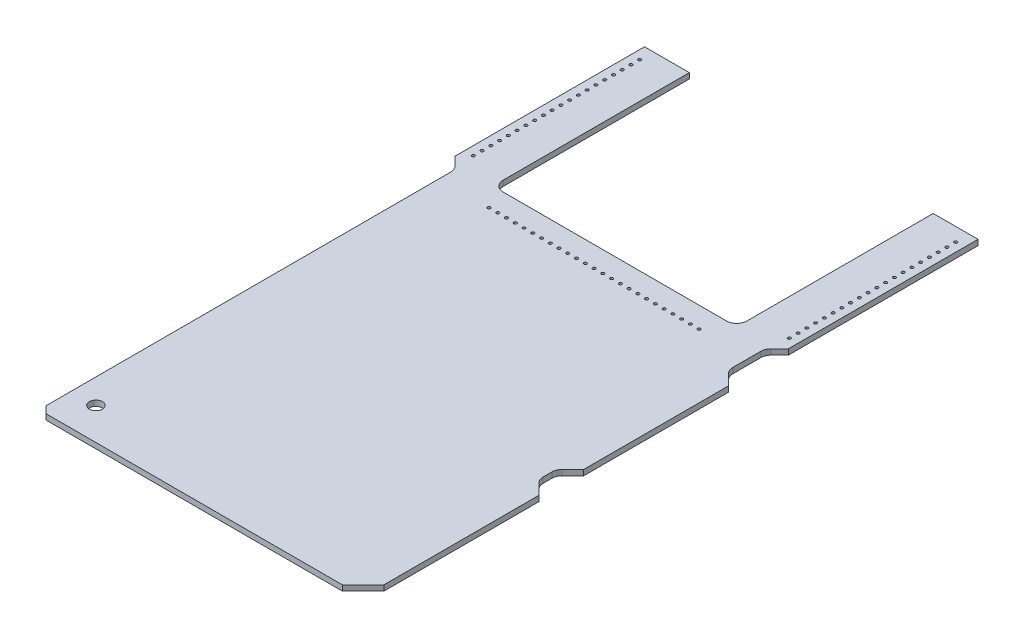
SolidWorks part; units mm, degrees
ref_plane "Front Plane" through (0, 0, 0) normal (0, 0, 1) x (1, 0, 0)
ref_plane "Top Plane" through (0, 0, 0) normal (0, 1, 0) x (1, 0, 0)
ref_plane "Right Plane" through (0, 0, 0) normal (1, 0, 0) x (0, 0, -1)
sketch "Sketch1" plane through (0, 0, 0) normal (0, 1, 0) x (1, 0, 0)
  line L1 (45, -88.5) -> (-45, -88.5)
  line L2 (45, -88.5) -> (45, 88.5)
  line L3 (45, 88.5) -> (-45, 88.5)
  line L4 (-45, -88.5) -> (-45, 88.5)
  line L5 (45, -88.5) -> (-45, 88.5) construction
  line L6 (45, 88.5) -> (-45, -88.5) construction
  point P0 (0, 0)
  dimension "D1" = 90
  dimension "D2" = 177
extrude "Boss-Extrude1" add sketch "Sketch1" along normal blind 1.6
sketch "Sketch5" plane through (0, 0, 0) normal (0, -1, 0) x (1, 0, 0)
  line L0 (45, 88.5) -> (45, -88.5) construction
  line L1 (37.6, -44) -> (37.6, -48)
  line L2 (37.6, -44) -> (22.4, -44)
  line L3 (22.4, -44) -> (22.4, -48)
  line L4 (37.6, -48) -> (22.4, -48)
  line L5 (16.1, -44) -> (16.1, -48)
  line L6 (16.1, -44) -> (0.9, -44)
  line L7 (0.9, -44) -> (0.9, -48)
  line L8 (16.1, -48) -> (0.9, -48)
  line L9 (37.6, -80) -> (37.6, -84)
  line L10 (37.6, -80) -> (22.4, -80)
  line L11 (22.4, -80) -> (22.4, -84)
  line L12 (37.6, -84) -> (22.4, -84)
  line L13 (12.1, -80) -> (12.1, -84)
  line L14 (12.1, -80) -> (-3.1, -80)
  line L15 (-3.1, -80) -> (-3.1, -84)
  line L16 (12.1, -84) -> (-3.1, -84)
  line L17 (2.025, -44.54) -> (14.975, -44.54)
  line L18 (2.025, -44.54) -> (2.025, -47.46)
  line L19 (2.025, -47.46) -> (14.975, -47.46)
  line L20 (14.975, -44.54) -> (14.975, -47.46)
  line L21 (23.525, -44.54) -> (36.475, -44.54)
  line L22 (23.525, -44.54) -> (23.525, -47.46)
  line L23 (23.525, -47.46) -> (36.475, -47.46)
  line L24 (36.475, -44.54) -> (36.475, -47.46)
  line L25 (-1.975, -80.54) -> (10.975, -80.54)
  line L26 (-1.975, -80.54) -> (-1.975, -83.46)
  line L27 (-1.975, -83.46) -> (10.975, -83.46)
  line L28 (10.975, -80.54) -> (10.975, -83.46)
  line L29 (23.525, -80.54) -> (36.475, -80.54)
  line L30 (23.525, -80.54) -> (23.525, -83.46)
  line L31 (23.525, -83.46) -> (36.475, -83.46)
  line L32 (36.475, -80.54) -> (36.475, -83.46)
  line L33 (-22, -41.5) -> (43, -41.5) construction
  line L34 (-22, -41.5) -> (-22, -86.5) construction
  line L35 (-22, -86.5) -> (43, -86.5) construction
  line L36 (43, -41.5) -> (43, -86.5) construction
  line L37 (45, -88.5) -> (-45, -88.5) construction
  point P16 (8.5, -44)
  point P17 (30, -44)
  point P18 (4.5, -84)
  point P19 (30, -84)
  point P25 (37.6, -82)
  point P26 (37.6, -46)
  point P38 (8.5, -44.54)
  point P39 (2.025, -46)
  point P40 (0.9, -46)
  point P41 (30, -44.54)
  point P42 (-1.975, -82)
  point P43 (-3.1, -82)
  point P44 (4.5, -83.46)
  point P45 (30, -83.46)
  dimension "D1" = 15.2
  dimension "D2" = 4
  dimension "D3" = 21.5
  dimension "D4" = 25.5
  dimension "D5" = 2.92
  dimension "D6" = 12.95
  dimension "D7" = 36
  dimension "D8" = 65
  dimension "D9" = 45
  dimension "D10" = 2.5
  dimension "D11" = 5.4
  dimension "D12" = 2
  dimension "D13" = 2
sketch "Sketch7" plane through (0, 0, 0) normal (0, -1, 0) x (1, 0, 0)
  line L0 (-45, -30.1257) -> (-48.3743, -33.5)
  line L1 (-45, -88.5) -> (-48.3743, -88.5)
  line L2 (-45, -88.5) -> (-45, -30.1257)
  line L4 (-48.3743, -88.5) -> (-48.3743, -33.5)
  line L5 (45, -88.5) -> (48.3743, -88.5)
  line L6 (45, -88.5) -> (45, -30.1257)
  line L8 (48.3743, -88.5) -> (48.3743, -33.5)
  line L9 (45, -30.1257) -> (48.3743, -33.5)
  line M9 (-45, 88.5) -> (-45, -88.5)
  line M11 (45, -88.5) -> (45, 88.5)
  dimension "D1" = 3.3743
  dimension "D2" = 55
  dimension "D3" = 45
extrude "Boss-Extrude4" add sketch "Sketch7" against normal up to surface (1.6 mm away) contours L4 L1 L0 M9 | L9 L5 L8 M11 region at (-46.6704, 0, -60.1481) region at (46.6704, 0, -60.1481) up to face at (0, 1.6, 0)
sketch "Sketch8" plane through (0, 1.6, 0) normal (0, 1, 0) x (1, 0, 0)
  line L0 (-30.48, 25.5) -> (30.48, 25.5) construction
  line L2 (48.3743, 88.5) -> (-48.3743, 88.5) construction
  circle A0 centre (-45.8343, 84.563) radius 0.4318 construction
  circle A1 centre (-45.8343, 84.563) radius 0.4318
  circle A2 centre (45.8343, 84.563) radius 0.4318 construction
  circle A3 centre (45.8343, 84.563) radius 0.4318
  circle A8 centre (-45.8343, 82.023) radius 0.4318
  circle A9 centre (45.8343, 82.023) radius 0.4318
  circle A10 centre (-45.8343, 79.483) radius 0.4318
  circle A11 centre (45.8343, 79.483) radius 0.4318
  circle A12 centre (-45.8343, 76.943) radius 0.4318
  circle A13 centre (45.8343, 76.943) radius 0.4318
  circle A14 centre (-45.8343, 74.403) radius 0.4318
  circle A15 centre (45.8343, 74.403) radius 0.4318
  circle A16 centre (-45.8343, 71.863) radius 0.4318
  circle A17 centre (45.8343, 71.863) radius 0.4318
  circle A18 centre (-45.8343, 69.323) radius 0.4318
  circle A19 centre (45.8343, 69.323) radius 0.4318
  circle A20 centre (-45.8343, 66.783) radius 0.4318
  circle A21 centre (45.8343, 66.783) radius 0.4318
  circle A22 centre (-45.8343, 64.243) radius 0.4318
  circle A23 centre (45.8343, 64.243) radius 0.4318
  circle A24 centre (-45.8343, 61.703) radius 0.4318
  circle A25 centre (45.8343, 61.703) radius 0.4318
  circle A26 centre (-45.8343, 59.163) radius 0.4318
  circle A27 centre (45.8343, 59.163) radius 0.4318
  circle A28 centre (-45.8343, 56.623) radius 0.4318
  circle A29 centre (45.8343, 56.623) radius 0.4318
  circle A30 centre (-45.8343, 54.083) radius 0.4318
  circle A31 centre (45.8343, 54.083) radius 0.4318
  circle A32 centre (-45.8343, 51.543) radius 0.4318
  circle A33 centre (45.8343, 51.543) radius 0.4318
  circle A34 centre (-45.8343, 49.003) radius 0.4318
  circle A35 centre (45.8343, 49.003) radius 0.4318
  circle A36 centre (-45.8343, 46.463) radius 0.4318
  circle A37 centre (45.8343, 46.463) radius 0.4318
  circle A38 centre (-45.8343, 43.923) radius 0.4318
  circle A39 centre (45.8343, 43.923) radius 0.4318
  circle A40 centre (-45.8343, 41.383) radius 0.4318
  circle A41 centre (45.8343, 41.383) radius 0.4318
  circle A42 centre (-45.8343, 38.843) radius 0.4318
  circle A43 centre (45.8343, 38.843) radius 0.4318
  circle A44 centre (-45.8343, 36.303) radius 0.4318
  circle A45 centre (45.8343, 36.303) radius 0.4318
  arc A46 (-37.846, -79.9277) -> (-37.846, -82.4123) centre (-37.846, -81.17) ccw construction
  arc A47 (-37.846, -79.9277) -> (-37.846, -82.4123) centre (-37.846, -81.17) ccw construction
  circle A48 centre (-37.846, -81.17) radius 1.9
  circle A49 centre (-30.48, 25.5) radius 0.4318
  circle A50 centre (-27.94, 25.5) radius 0.4318
  circle A51 centre (-25.4, 25.5) radius 0.4318
  circle A52 centre (-22.86, 25.5) radius 0.4318
  circle A53 centre (-20.32, 25.5) radius 0.4318
  circle A54 centre (-17.78, 25.5) radius 0.4318
  circle A55 centre (-15.24, 25.5) radius 0.4318
  circle A56 centre (-12.7, 25.5) radius 0.4318
  circle A57 centre (-10.16, 25.5) radius 0.4318
  circle A58 centre (-7.62, 25.5) radius 0.4318
  circle A59 centre (-5.08, 25.5) radius 0.4318
  circle A60 centre (-2.54, 25.5) radius 0.4318
  circle A61 centre (0, 25.5) radius 0.4318
  circle A62 centre (2.54, 25.5) radius 0.4318
  circle A63 centre (5.08, 25.5) radius 0.4318
  circle A64 centre (7.62, 25.5) radius 0.4318
  circle A65 centre (10.16, 25.5) radius 0.4318
  circle A66 centre (12.7, 25.5) radius 0.4318
  circle A67 centre (15.24, 25.5) radius 0.4318
  circle A68 centre (17.78, 25.5) radius 0.4318
  circle A69 centre (20.32, 25.5) radius 0.4318
  circle A70 centre (22.86, 25.5) radius 0.4318
  circle A71 centre (25.4, 25.5) radius 0.4318
  circle A72 centre (27.94, 25.5) radius 0.4318
  circle A73 centre (30.48, 25.5) radius 0.4318
  point P129 (0, 0)
  dimension "D3" = 3.8
  dimension "D2" = 2.54
  dimension "D5" = 2.54
  dimension "D6" = 63
  dimension "D1" = 20
  dimension "D4" = 25
extrude "Cut-Extrude1" cut sketch "Sketch8" against normal through all
extrude "Cut-Extrude2" [suppressed] cut sketch "Sketch5" against normal through all
sketch "w" plane through (0, 1.6, 0) normal (0, 1, 0) x (1, 0, 0)
  line L0 (45, -88.5) -> (49, -84.5)
  line L1 (45, -88.5) -> (45, 30.1257) construction
  line L2 (49, -84.5) -> (49, -39.5)
  line L3 (49, -39.5) -> (45, -35.5)
  line L4 (45, -30.5) -> (49, -26.5)
  line L5 (49, -26.5) -> (49, 15.5)
  line L6 (49, 15.5) -> (45, 19.5)
  line L7 (45, 19.5) -> (45, -30.5)
  line L8 (45, -35.5) -> (45, -88.5)
  line L9 (-45, -88.5) -> (45, -88.5) construction
  line L10 (-45, -88.5) -> (-43, -90.5)
  line L11 (-43, -90.5) -> (43, -90.5)
  line L12 (43, -90.5) -> (45, -88.5)
  line L13 (-45, -88.5) -> (45, -88.5)
  dimension "D1" = 4
  dimension "D2" = 45
  dimension "D3" = 53
  dimension "D4" = 50
  dimension "D5" = 5
  dimension "D6" = 2
extrude "Boss-Extrude5" add sketch "w" against normal up to surface (1.6 mm away) contours L11 L12 L10 | L2 L3 L0 | L5 L6 L4 region at (46.9456, 1.6, 62) region at (0, 1.6, 89.4924) region at (46.942, 1.6, 5.5) up to face at (-12.7, 0, -25.0682)
sketch "Sketch9" plane through (0, 0, 0) normal (0, -1, 0) x (1, 0, 0)
  line L0 (48.3743, -88.5) -> (-48.3743, -88.5) construction
  line L1 (-35.3743, -88.5) -> (35.3743, -88.5)
  line L2 (-35.3743, -88.5) -> (-35.3743, -31.5)
  line L3 (-35.3743, -31.5) -> (35.3743, -31.5)
  line L4 (35.3743, -88.5) -> (35.3743, -31.5)
  line L5 (48.3743, -88.5) -> (48.3743, -33.5) construction
  line L6 (-48.3743, -88.5) -> (-48.3743, -33.5) construction
  dimension "D1" = 13
  dimension "D2" = 13
  dimension "D3" = 57
extrude "Cut-Extrude3" cut sketch "Sketch9" against normal through all
fillet "Fillet1" radius 3 7 edges at (45, 0.8, -30.1257) (-45, 0.8, -30.1257) (45, 0.8, -19.5) (45, 0.8, 30.5) (45, 0.8, 35.5) (-35.3743, 0.8, -31.5) (35.3743, 0.8, -31.5)
